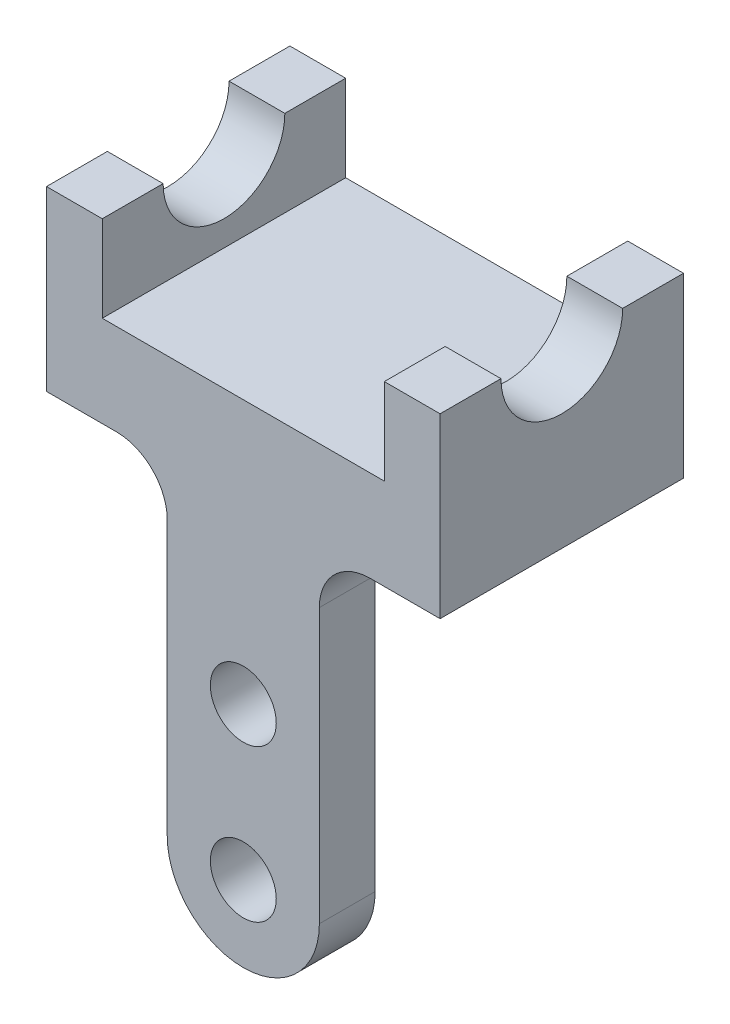
SolidWorks part; units mm, degrees
ref_plane "Front Plane" through (0, 0, 0) normal (0, 0, 1) x (1, 0, 0)
ref_plane "Top Plane" through (0, 0, 0) normal (0, 1, 0) x (1, 0, 0)
ref_plane "Right Plane" through (0, 0, 0) normal (1, 0, 0) x (0, 0, -1)
sketch "Sketch1" plane through (0, 0, 0) normal (0, 0, 1) x (1, 0, 0)
  line L0 (0, 87.1747) -> (0, -31.492) construction
  line L1 (15, 0) -> (15, 54)
  line L2 (25, 64) -> (38.8108, 64)
  line L3 (38.8108, 64) -> (38.8108, 99)
  line L4 (38.8108, 99) -> (27.8108, 99)
  line L5 (27.8108, 99) -> (27.8108, 82)
  line L6 (27.8108, 82) -> (-27.8108, 82)
  line L7 (-27.8108, 99) -> (-27.8108, 82)
  line L8 (-38.8108, 99) -> (-27.8108, 99)
  line L9 (-38.8108, 64) -> (-38.8108, 99)
  line L10 (-25, 64) -> (-38.8108, 64)
  line L11 (-15, 0) -> (-15, 54)
  line L12 (25, 64) -> (-25, 64)
  arc A0 (-15, 0) -> (15, 0) centre (0, 0) ccw
  circle A1 centre (0, 0) radius 6.5
  circle A2 centre (0, 30) radius 6.5
  arc A3 (15, 54) -> (25, 64) centre (25, 54) cw
  arc A4 (-15, 54) -> (-25, 64) centre (-25, 54) ccw
  point P22 (0, 82)
  dimension "D1" = 10
  dimension "D3" = 30
  dimension "D4" = 13
  dimension "D5" = 13
  dimension "D2" = 30
  dimension "D6" = 64
  dimension "D7" = 38.8108
  dimension "D8" = 35
  dimension "D9" = 18
  dimension "D10" = 11
extrude "Boss-Extrude1" add sketch "Sketch1" against normal blind 11 contours L12 L0 A2 A1 A0 L1 A3 | L0 L12 A4 L11 A0 A1 A2 region at (8.122, 28.2118, 0) region at (-8.122, 28.2118, 0)
extrude "Boss-Extrude2" add sketch "Sketch1<3>" against normal blind 48 contours L6 L0 L12 L2 L3 L4 L5 | L0 L6 L7 L8 L9 L10 L12 region at (22.3416, 76.6953, 0) region at (-22.3416, 76.6953, 0)
sketch "Sketch1<3>" plane through (0, 0, 0) normal (0, 0, 1) x (1, 0, 0) same geometry as "Sketch1"
sketch "Sketch2" plane through (38.8108, 0, 0) normal (1, 0, 0) x (0, 0, -1)
  line L0 (48, 99) -> (0, 99) construction
  line L1 (0, 64) -> (0, 99) construction
  circle A0 centre (24, 99) radius 12
  dimension "D1" = 24
  dimension "D2" = 24
extrude "Cut-Extrude1" cut sketch "Sketch2" against normal through all
